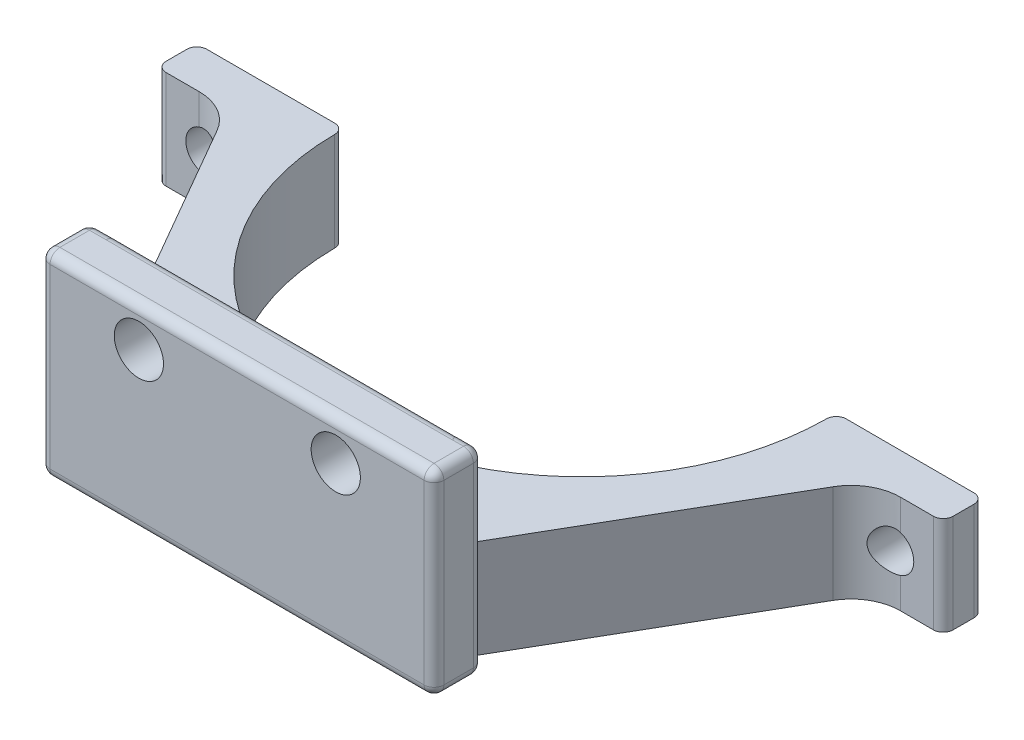
SolidWorks part; units mm, degrees
ref_plane "前视基准面" through (0, 0, 0) normal (0, 0, 1) x (1, 0, 0)
ref_plane "上视基准面" through (0, 0, 0) normal (0, 1, 0) x (1, 0, 0)
ref_plane "右视基准面" through (0, 0, 0) normal (1, 0, 0) x (0, 0, -1)
sketch "草图1" plane through (0, 0, 0) normal (0, 1, 0) x (1, 0, 0)
  line L0 (17.2972, -30.0134) -> (-17.3438, -29.9865)
  line L3 (-31.3213, -5.7333) -> (-17.3438, -29.9865)
  line L5 (17.2972, -30.0134) -> (31.3124, -5.7819)
  line L6 (17.305, -30) -> (19.9767, -30)
  line L9 (-39, 0.885) -> (-25.9997, 0.885)
  line L38 (-40, -0.115) -> (-40, -2.2299)
  line L39 (-39, -3.2299) -> (-35.6534, -3.2299)
  line L41 (38.9949, -3.2905) -> (35.6483, -3.2853)
  line L42 (39.9998, -0.1771) -> (39.9965, -2.292)
  line L44 (39.0013, 0.8245) -> (26.0011, 0.8447)
  line L46 (34.641, -0.0269) -> (34.146, 0.832) [skipped]
  line L47 (19.9767, -30) -> (19.9767, -35)
  line L48 (19.9767, -35) -> (-20.0233, -35)
  line L49 (-20.0233, -35) -> (-20.0233, -30)
  line L50 (-17.3438, -29.9865) -> (-20.0233, -30)
  line L51 (14.4571, 29.9888) -> (-14.4105, 30.0112) [skipped]
  line L52 (-18.7425, 27.5146) -> (-23.0888, 20) [skipped]
  line L53 (-0.0233, -30) -> (17.2972, -30.0134) [skipped]
  arc A0 (-24.9998, -0.1105) -> (-25.9997, 0.885) centre (-25.9997, -0.115) ccw
  arc A1 (-40, -2.2299) -> (-39, -3.2299) centre (-39, -2.2299) ccw
  arc A2 (-24.9998, -0.1105) -> (24.9996, -0.1494) centre (0, 0) ccw
  arc A3 (-39, 0.885) -> (-40, -0.115) centre (-39, -0.115) ccw
  arc A4 (39.9965, -2.292) -> (38.9949, -3.2905) centre (38.9965, -2.2905) cw
  arc A5 (31.3124, -5.7819) -> (35.6483, -3.2853) centre (35.6406, -8.2853) cw
  arc A6 (-31.3213, -5.7333) -> (-35.6534, -3.2299) centre (-35.6534, -8.2299) ccw
  arc A7 (39.9998, -0.1771) -> (39.0013, 0.8245) centre (38.9998, -0.1755) ccw
  arc A8 (24.9996, -0.1494) -> (26.0011, 0.8447) centre (25.9995, -0.1553) cw
  dimension "D1" = 5
  dimension "D2" = 1
  dimension "D3" = 1
extrude "凸台-拉伸2" add sketch "草图1" along normal blind 10 contours A8 A2 A0 L9 A3 L38 A1 L39 A6 L3 L50 L49 L48 L47 L6 L5 A5 L41 A4 L42 A7 L44 | L0 L50 L49 L48 L47 L6 L5 region at (-0.0384, 0, 32.4998) region at (8.6376, 0, 29.1491)
sketch "草图2" plane through (0, 0, 0) normal (0, 0, 1) x (1, 0, 0)
  line L0 (0, 0) -> (0, 5)
  line L1 (0, 5) -> (-35, 5)
  line L2 (-35, 5) -> (35, 5)
  circle A0 centre (-35, 5) radius 2
  circle A1 centre (35, 5) radius 2
extrude "切除-拉伸1" cut sketch "草图2" along normal through all and the other way through all contours A1 | A0 region at (-36.9434, 5, 0) region at (35, 6.9434, 0)
extrude "凸台-拉伸4" add sketch "草图1<6>" along normal blind 20 contours L0 L50 L49 L48 L47 L6 L5 region at (-0.0384, 0, 32.4998)
sketch "草图1<6>" plane through (0, 0, 0) normal (0, 1, 0) x (1, 0, 0) same geometry as "草图1"
sketch "草图4" plane through (0, 0, 35) normal (0, 0, 1) x (1, 0, 0)
  line L0 (0, 0) -> (0, 16)
  line L1 (0, 16) -> (10, 16)
  line L2 (0, 16) -> (-10, 16)
  circle A0 centre (-10, 16) radius 2.5
  circle A1 centre (10, 16) radius 2.5
extrude "切除-拉伸2" cut sketch "草图4" against normal blind 20 contours A0 | A1 region at (10, 18.4293, 35) region at (-12.4293, 16, 35)
fillet "圆角1" radius 1 16 edges at (-20.0233, 10, 30) (-20.0233, 10, 35) (-20.0233, 0, 32.5) (19.9767, 10, 35) (19.9767, 10, 30) (19.9767, 0, 32.5) (17.3011, 20, 30.0067) (18.6408, 20, 30) (19.9767, 20, 32.5) (-0.0233, 20, 35) (-20.0233, 20, 32.5) (-18.6836, 20, 29.9933) (-0.0233, 20, 30) (-18.6836, 0, 29.9933) (18.6408, 0, 30) (-0.0233, 0, 35)
